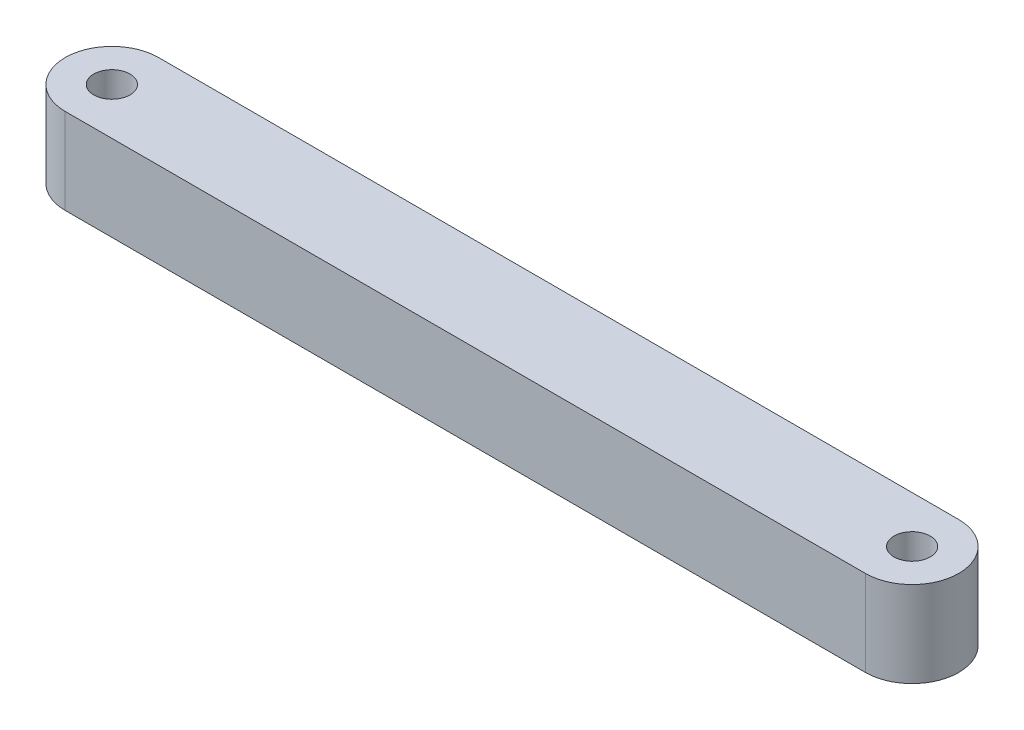
SolidWorks part; units mm, degrees
ref_plane "Front Plane" through (0, 0, 0) normal (0, 0, 1) x (1, 0, 0)
ref_plane "Top Plane" through (0, 0, 0) normal (0, 1, 0) x (1, 0, 0)
ref_plane "Right Plane" through (0, 0, 0) normal (1, 0, 0) x (0, 0, -1)
sketch "Sketch1" plane through (0, 0, 0) normal (0, 1, 0) x (1, 0, 0)
  line L0 (0, 0) -> (95.25, 0) construction
  line L1 (0, 5.5563) -> (95.25, 5.5563)
  line L2 (0, -5.5563) -> (95.25, -5.5563)
  arc A1 (0, 5.5563) -> (0, -5.5563) centre (0, 0) ccw
  arc A2 (95.25, -5.5563) -> (95.25, 5.5563) centre (95.25, 0) ccw
  point P3 (47.625, 0)
  dimension "D1" = 11.1125
  dimension "D2" = 95.25
extrude "Boss-Extrude1" add sketch "Sketch1" along normal blind 10.2108
sketch "Sketch2" plane through (0, 10.2108, 0) normal (0, 1, 0) x (1, 0, 0)
  circle A1 centre (95.25, 0) radius 2.159
  circle A2 centre (0, 0) radius 2.159
  dimension "D3" = 4.318
  dimension "D1" = 95.25
extrude "Cut-Extrude1" cut sketch "Sketch2" against normal through all
ref_plane "Plane1" through (0, 5.1054, 0) normal (0, 1, 0) x (1, 0, 0)
